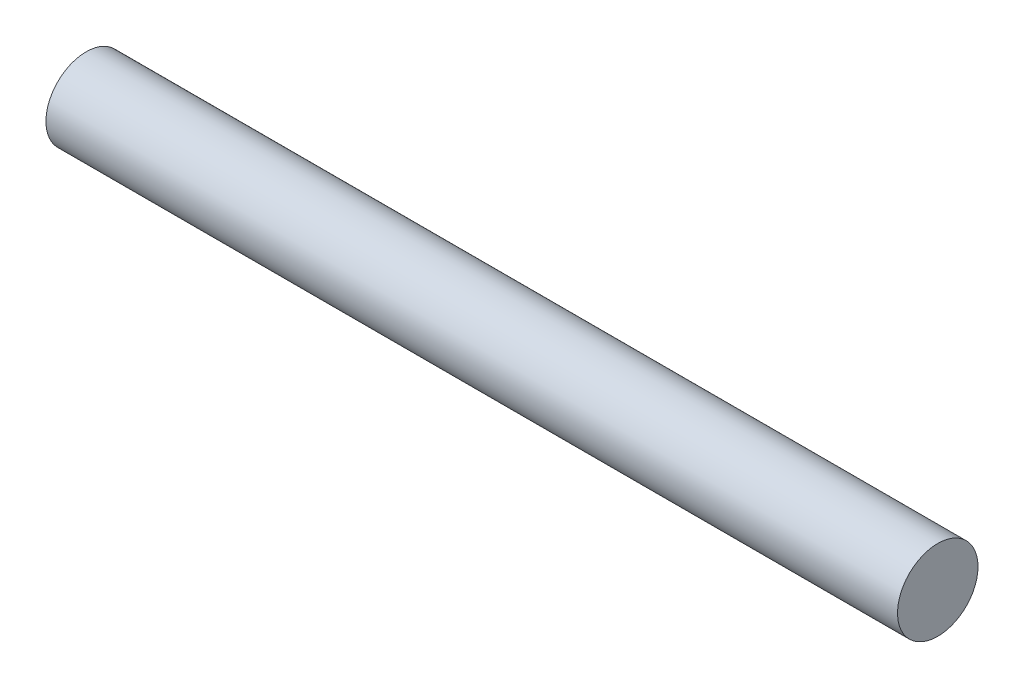
SolidWorks part; units mm, degrees
material "6061 Alloy"
ref_plane "Front Plane" through (0, 0, 0) normal (0, 0, 1) x (1, 0, 0)
ref_plane "Top Plane" through (0, 0, 0) normal (0, 1, 0) x (1, 0, 0)
ref_plane "Right Plane" through (0, 0, 0) normal (1, 0, 0) x (0, 0, -1)
sketch "Sketch1" plane through (0, 0, 0) normal (1, 0, 0) x (0, 0, -1)
  circle A0 centre (0, 0) radius 3
  dimension "D1" = 6
extrude "Boss-Extrude1" add sketch "Sketch1" along normal blind 63.5
